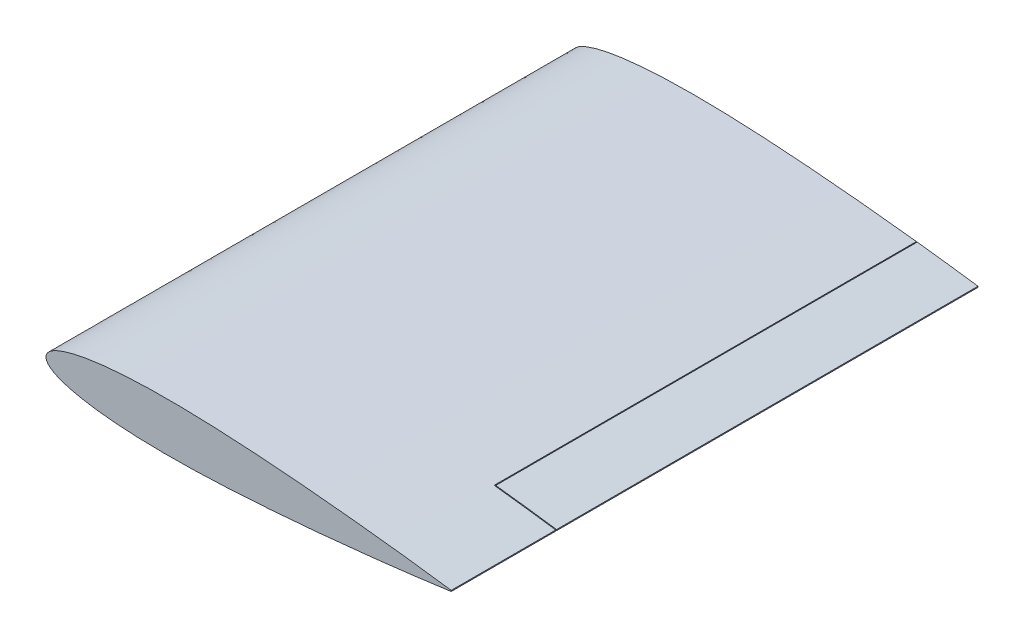
SolidWorks part; units mm, degrees
material "AFL blue foam"
ref_plane "Front Plane" through (0, 0, 0) normal (0, 0, 1) x (1, 0, 0)
ref_plane "Top Plane" through (0, 0, 0) normal (0, 1, 0) x (1, 0, 0)
ref_plane "Right Plane" through (0, 0, 0) normal (1, 0, 0) x (0, 0, -1)
curve "Curve1"
  spline degree 3 poles (0, 0, 0) (0.003, 0.0365, 0) (0.009, 0.1114, 0) (0.0578, 0.22, 0) (0.134, 0.3245, 0) (0.2397, 0.4254, 0) (0.3736, 0.523, 0) (0.536, 0.6174, 0) (0.7264, 0.7086, 0) (0.9445, 0.7962, 0) (1.1898, 0.8801, 0) (1.462, 0.96, 0) (1.7603, 1.0355, 0) (2.0841, 1.1065, 0) (2.4327, 1.1725, 0) (2.8052, 1.2334, 0) (3.2008, 1.2888, 0) (3.6185, 1.3388, 0) (4.0575, 1.3829, 0) (4.5166, 1.4212, 0) (4.9948, 1.4535, 0) (5.491, 1.4798, 0) (6.0041, 1.5001, 0) (6.5327, 1.5144, 0) (7.0758, 1.5227, 0) (7.632, 1.5254, 0) (8.2001, 1.5224, 0) (8.7786, 1.514, 0) (9.3663, 1.5004, 0) (9.9618, 1.4819, 0) (10.5636, 1.4587, 0) (11.1705, 1.4311, 0) (11.7809, 1.3995, 0) (12.3935, 1.3642, 0) (13.0067, 1.3254, 0) (13.6193, 1.2836, 0) (14.2297, 1.2391, 0) (14.8366, 1.1921, 0) (15.4384, 1.1431, 0) (16.0339, 1.0922, 0) (16.6216, 1.0399, 0) (17.2001, 0.9864, 0) (17.7681, 0.9321, 0) (18.3242, 0.8771, 0) (18.8673, 0.8219, 0) (19.3959, 0.7666, 0) (19.9089, 0.7116, 0) (20.405, 0.657, 0) (20.8832, 0.6033, 0) (21.3422, 0.5505, 0) (21.7811, 0.499, 0) (22.1987, 0.449, 0) (22.5942, 0.4008, 0) (22.9666, 0.3545, 0) (23.3149, 0.3106, 0) (23.6385, 0.2691, 0) (23.9366, 0.2304, 0) (24.2084, 0.1946, 0) (24.4533, 0.1619, 0) (24.6708, 0.1326, 0) (24.8603, 0.1068, 0) (25.0214, 0.0847, 0) (25.1537, 0.0664, 0) (25.257, 0.052, 0) (25.3309, 0.0417, 0) (25.3753, 0.0355, 0) (25.3951, 0.0327, 0) (25.4, 0.032, 0) knots 0 0 0 0 0.004218 0.008652 0.013562 0.019137 0.0255 0.032726 0.040862 0.04993 0.05994 0.070892 0.082777 0.095581 0.109286 0.123868 0.139301 0.155557 0.172602 0.190404 0.208924 0.228125 0.247965 0.268401 0.289388 0.310881 0.332832 0.35519 0.377906 0.400928 0.424203 0.447679 0.471299 0.49501 0.518757 0.542484 0.566136 0.589657 0.612992 0.636087 0.658886 0.681338 0.703388 0.724985 0.746079 0.766619 0.786556 0.805845 0.82444 0.842296 0.859372 0.875627 0.891023 0.905523 0.919093 0.9317 0.943314 0.953909 0.963457 0.971937 0.979328 0.985613 0.990775 0.994804 0.997688 0.999422 1 1 1 1
curve "Curve2"
  spline degree 3 poles (0.0148, -0.1082, 0) (0.028, -0.1443, 0) (0.0559, -0.2205, 0) (0.1346, -0.3244, 0) (0.2395, -0.4254, 0) (0.3737, -0.523, 0) (0.536, -0.6174, 0) (0.7264, -0.7086, 0) (0.9445, -0.7962, 0) (1.1898, -0.8801, 0) (1.462, -0.96, 0) (1.7603, -1.0355, 0) (2.0841, -1.1065, 0) (2.4327, -1.1725, 0) (2.8052, -1.2334, 0) (3.2008, -1.2888, 0) (3.6185, -1.3388, 0) (4.0575, -1.3829, 0) (4.5166, -1.4212, 0) (4.9948, -1.4535, 0) (5.491, -1.4798, 0) (6.0041, -1.5001, 0) (6.5327, -1.5144, 0) (7.0758, -1.5227, 0) (7.632, -1.5254, 0) (8.2001, -1.5224, 0) (8.7786, -1.514, 0) (9.3663, -1.5004, 0) (9.9618, -1.4819, 0) (10.5636, -1.4587, 0) (11.1705, -1.4311, 0) (11.7809, -1.3995, 0) (12.3935, -1.3642, 0) (13.0067, -1.3254, 0) (13.6193, -1.2836, 0) (14.2297, -1.2391, 0) (14.8366, -1.1921, 0) (15.4384, -1.1431, 0) (16.0339, -1.0922, 0) (16.6216, -1.0399, 0) (17.2001, -0.9864, 0) (17.7681, -0.9321, 0) (18.3242, -0.8771, 0) (18.8673, -0.8219, 0) (19.3959, -0.7666, 0) (19.9089, -0.7116, 0) (20.405, -0.657, 0) (20.8832, -0.6033, 0) (21.3422, -0.5505, 0) (21.7811, -0.499, 0) (22.1987, -0.449, 0) (22.5942, -0.4008, 0) (22.9666, -0.3545, 0) (23.3149, -0.3106, 0) (23.6385, -0.2691, 0) (23.9366, -0.2304, 0) (24.2084, -0.1946, 0) (24.4533, -0.1619, 0) (24.6708, -0.1326, 0) (24.8603, -0.1068, 0) (25.0214, -0.0847, 0) (25.1537, -0.0664, 0) (25.257, -0.052, 0) (25.3309, -0.0417, 0) (25.3753, -0.0355, 0) (25.3951, -0.0327, 0) (25.4, -0.032, 0) knots 0 0 0 0 0.004453 0.009384 0.014983 0.021372 0.028629 0.036799 0.045906 0.055959 0.066957 0.078892 0.091751 0.105513 0.120157 0.135656 0.15198 0.169098 0.186975 0.205574 0.224856 0.24478 0.265302 0.286379 0.307962 0.330006 0.352459 0.375271 0.398391 0.421765 0.445339 0.46906 0.492871 0.516719 0.540546 0.564298 0.587919 0.611353 0.634545 0.657442 0.679988 0.702132 0.723821 0.745003 0.76563 0.785652 0.805023 0.823696 0.841628 0.858776 0.8751 0.890561 0.905123 0.91875 0.93141 0.943074 0.953713 0.963302 0.971818 0.979241 0.985552 0.990736 0.994782 0.997678 0.999419 1 1 1 1
sketch "Sketch1" plane through (0, 0, 0) normal (0, 0, 1) x (1, 0, 0)
  line L0 (0, 0) -> (0.0742, -0.5411)
  line L1 (127, 0.16) -> (127, -0.16)
  spline S2 degree 3 poles (0.0742, -0.5411) (0.1402, -0.7217) (0.2794, -1.1023) (0.673, -1.6219) (1.1974, -2.1272) (1.8685, -2.615) (2.6798, -3.0872) (3.6318, -3.5429) (4.7223, -3.9812) (5.9492, -4.4007) (7.31, -4.8) (8.8016, -5.1777) (10.4206, -5.5323) (12.1634, -5.8624) (14.0259, -6.1668) (16.0039, -6.4442) (18.0926, -6.6938) (20.2874, -6.9146) (22.583, -7.106) (24.9741, -7.2675) (27.4552, -7.3989) (30.0204, -7.5003) (32.6637, -7.5718) (35.3791, -7.6137) (38.1601, -7.6269) (41.0003, -7.6119) (43.8929, -7.5699) (46.8314, -7.5019) (49.8088, -7.4093) (52.8181, -7.2933) (55.8524, -7.1556) (58.9045, -6.9976) (62.9897, -6.7619) (67.0743, -6.4928) (72.1532, -6.1221) (77.1616, -5.7236) (82.1152, -5.2913) (86.9285, -4.8463) (91.5567, -4.3963) (96.0742, -3.9303) (100.3424, -3.4723) (104.3213, -3.0299) (108.8003, -2.5098) (112.8562, -2.0199) (115.9539, -1.6325) (118.1927, -1.3456) (120.4545, -1.0515) (122.9821, -0.715) (125.1839, -0.4131) (126.3836, -0.2463) (126.7779, -0.1912) (127, -0.16) knots 0 0 0 0 0.004453 0.009384 0.014983 0.021372 0.028629 0.036799 0.045906 0.055959 0.066957 0.078892 0.091751 0.105513 0.120157 0.135656 0.15198 0.169098 0.186975 0.205574 0.224856 0.24478 0.265302 0.286379 0.307962 0.330006 0.352459 0.375271 0.398391 0.421765 0.445339 0.46906 0.492871 0.540546 0.564298 0.611353 0.657442 0.679988 0.723821 0.76563 0.785652 0.823696 0.858776 0.890561 0.91875 0.93141 0.943074 0.971818 0.990736 0.994782 1 1 1 1
  spline S3 degree 3 poles (0, 0) (0.0148, 0.1826) (0.0451, 0.5571) (0.2892, 1.1001) (0.6698, 1.6226) (1.1984, 2.127) (1.8682, 2.615) (2.6799, 3.0872) (3.6318, 3.5429) (4.7223, 3.9812) (5.9492, 4.4007) (7.31, 4.8) (8.8016, 5.1777) (10.4206, 5.5323) (12.1634, 5.8624) (14.0259, 6.1668) (16.0039, 6.4442) (18.0926, 6.6938) (20.2874, 6.9146) (22.583, 7.106) (24.9741, 7.2675) (27.4552, 7.3989) (30.0204, 7.5003) (32.6637, 7.5718) (35.3791, 7.6137) (38.1601, 7.6269) (41.0003, 7.6119) (43.8929, 7.5699) (46.8314, 7.5019) (49.8088, 7.4093) (52.8181, 7.2933) (55.8524, 7.1556) (58.9045, 6.9976) (62.9897, 6.7619) (67.0743, 6.4928) (72.1532, 6.1221) (77.1616, 5.7236) (82.1152, 5.2913) (86.9285, 4.8463) (91.5567, 4.3963) (96.0742, 3.9303) (100.3424, 3.4723) (104.3213, 3.0299) (108.8003, 2.5098) (112.8562, 2.0199) (115.9539, 1.6325) (118.1927, 1.3456) (120.4545, 1.0515) (122.9821, 0.715) (125.1839, 0.4131) (126.3836, 0.2463) (126.7779, 0.1912) (127, 0.16) knots 0 0 0 0 0.004218 0.008652 0.013562 0.019137 0.0255 0.032726 0.040862 0.04993 0.05994 0.070892 0.082777 0.095581 0.109286 0.123868 0.139301 0.155557 0.172602 0.190404 0.208924 0.228125 0.247965 0.268401 0.289388 0.310881 0.332832 0.35519 0.377906 0.400928 0.424203 0.447679 0.471299 0.49501 0.542484 0.566136 0.612992 0.658886 0.681338 0.724985 0.766619 0.786556 0.82444 0.859372 0.891023 0.919093 0.9317 0.943314 0.971937 0.990775 0.994804 1 1 1 1
  point P0 (127, 0)
  dimension "D1" = 127
extrude "Boss-Extrude1" add sketch "Sketch1" along normal blind 165.1
sketch "Sketch2" plane through (0, 0, 0) normal (0, 1, 0) x (1, 0, 0)
  line L0 (127, -165.1) -> (127, 0) construction
  line L1 (107.95, 0) -> (127, 0)
  line L2 (107.95, 0) -> (107.95, -132.08)
  line L3 (107.95, -132.08) -> (127, -132.08)
  line L4 (127, 0) -> (127, -132.08)
  dimension "D1" = 132.08
  dimension "D2" = 19.05
extrude "Cut-Extrude-Thin1" cut sketch "Sketch2" against normal blind 25.4 and the other way blind 25.4 thin thin type one direction wall 0.254
equation "\"span\"= 48"
equation "\"wing_chord\"= 9"
equation "\"fuse_len\"= 15"
equation "\"fuse_height\"= 5"
equation "\"fuse_wid\"= 5"
equation "\"foam_t\"= 0.1875"
equation "\"main_spar_len\"= 36"
equation "\"x_fuse_to_wing\"= 3"
equation "\"x_cg_from_le\"= 2.25"
equation "\"boom_len\"= 30"
equation "\"wing_angle\"= 1.5"
equation "\"boom_d\"= 0.75"
equation "\"wing_spar_d\"= 0.375"
equation "\"wing_spar_l\"= 48"
equation "\"wing_spar_spacing\"= 1.35"
equation "\"wing_mount_l\"= 2.5"
equation "\"vstab_span\"= 6.5"
equation "\"hstab_span\"= 15.25"
equation "\"tail_chord\"= 5"
equation "\"D1@Boss-Extrude1\"= \"vstab_span\""
equation "\"D1@Sketch2\"=\"vstab_span\"*0.8"
equation "\"D2@Sketch2\"=\"tail_chord\"*0.15"
